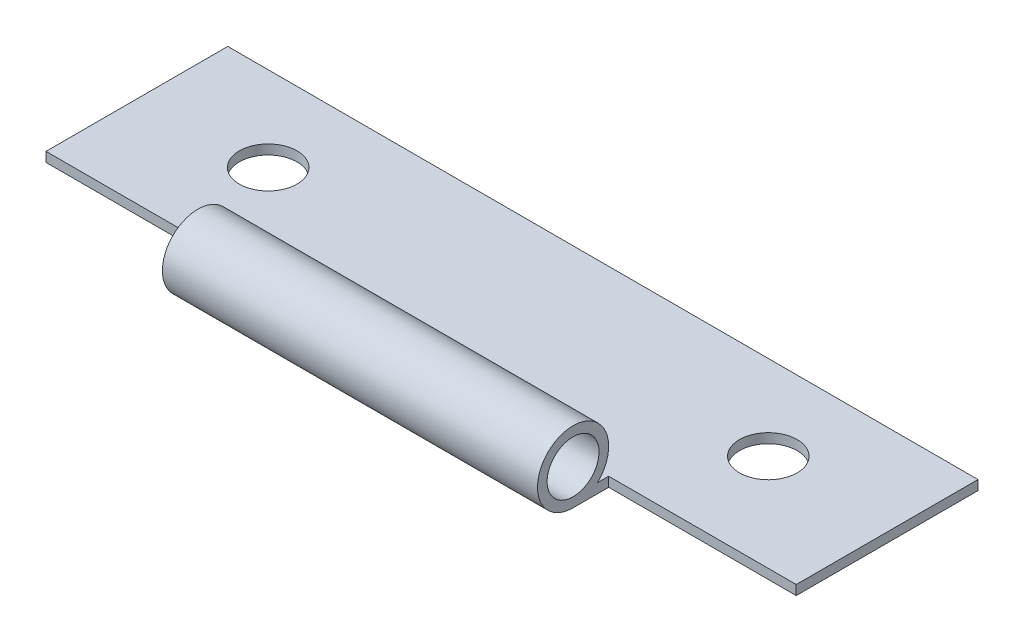
SolidWorks part; units mm, degrees
material "Latón"
ref_plane "Alzado" through (0, 0, 0) normal (0, 0, 1) x (1, 0, 0)
ref_plane "Planta" through (0, 0, 0) normal (0, 1, 0) x (1, 0, 0)
ref_plane "Vista lateral" through (0, 0, 0) normal (1, 0, 0) x (0, 0, -1)
sketch "Croquis1" plane through (0, 0, 0) normal (0, 1, 0) x (1, 0, 0)
  line L0 (19.5, 11.3) -> (19.5, 0) construction
  line L1 (0, 0) -> (39, 0)
  line L2 (0, 0) -> (0, 11.3)
  line L3 (0, 11.3) -> (39, 11.3)
  line L4 (39, 0) -> (39, 11.3)
  circle A0 centre (6.5, 6.9) radius 1.5
  circle A1 centre (32.5, 6.9) radius 1.5
  dimension "D3" = 3
  dimension "D1" = 39
  dimension "D2" = 11.3
  dimension "D4" = 4.4
  dimension "D5" = 26
extrude "Saliente-Extruir1" add sketch "Croquis1" along normal blind 0.5
sketch "Croquis2" plane through (39, 0, 0) normal (1, 0, 0) x (0, 0, -1)
  circle A0 centre (0, 1.85) radius 1.85
  circle A1 centre (0, 1.85) radius 1.35
  dimension "D1" = 3.7
extrude "Saliente-Extruir2" add sketch "Croquis2" against normal up to surface (39 mm away) up to face at (0, 0.25, -5.65)
sketch "Croquis3" plane through (0, 0, 0) normal (0, -1, 0) x (1, 0, 0)
  line L1 (0, -1.85) -> (39, -1.85) construction
  line L2 (29.25, -1.85) -> (39, -1.85)
  line L3 (29.25, -1.85) -> (29.25, 1.85)
  line L4 (29.25, 1.85) -> (39, 1.85)
  line L6 (39, -1.85) -> (39, 1.85)
  line L7 (39, 1.85) -> (0, 1.85) construction
  line L9 (9.75, 1.85) -> (0, 1.85)
  line L10 (9.75, 1.85) -> (9.75, -1.85)
  line L11 (9.75, -1.85) -> (0, -1.85)
  line L12 (0, 1.85) -> (0, -1.85)
  line L13 (0, -11.3) -> (0, -1.2649) construction
  dimension "D1" = 19.5
extrude "Cortar-Extruir1" cut sketch "Croquis3" against normal through all
